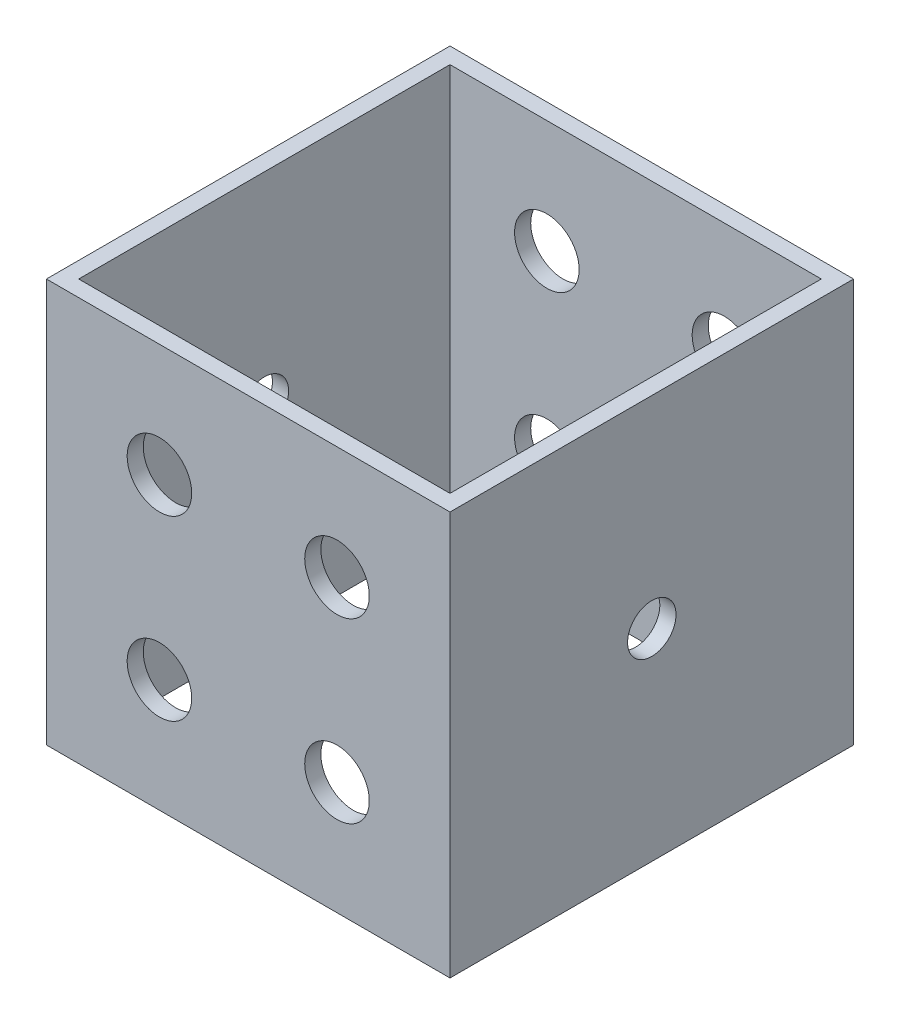
SolidWorks part; units mm, degrees
ref_plane "Front Plane" through (0, 0, 0) normal (0, 0, 1) x (1, 0, 0)
ref_plane "Top Plane" through (0, 0, 0) normal (0, 1, 0) x (1, 0, 0)
ref_plane "Right Plane" through (0, 0, 0) normal (1, 0, 0) x (0, 0, -1)
sketch "Sketch1" plane through (0, 0, 0) normal (0, 1, 0) x (1, 0, 0)
  line L0 (0, 43.992) -> (0, -43.1735) construction
  line L1 (-56.8827, 0) -> (56.8827, 0) construction
  line L3 (-11.5, 11.5) -> (11.5, 11.5)
  line L4 (-11.5, 11.5) -> (-11.5, -11.5)
  line L5 (-11.5, -11.5) -> (11.5, -11.5)
  line L6 (11.5, 11.5) -> (11.5, -11.5)
  line L7 (-11.5, 11.5) -> (11.5, -11.5) construction
  line L8 (-11.5, -11.5) -> (11.5, 11.5) construction
  line L9 (-12.5, 12.5) -> (12.5, 12.5)
  line L10 (-12.5, 12.5) -> (-12.5, -12.5)
  line L11 (-12.5, -12.5) -> (12.5, -12.5)
  line L12 (12.5, 12.5) -> (12.5, -12.5)
  line L13 (-12.5, 12.5) -> (12.5, -12.5) construction
  line L14 (-12.5, -12.5) -> (12.5, 12.5) construction
  point P5 (0, 0)
  point P10 (0, 0)
extrude "Boss-Extrude1" add sketch "Sketch1" along normal blind 12.5 and the other way blind 12.5
sketch "Sketch2" plane through (0, 0, -12.5) normal (0, 0, -1) x (-1, 0, 0)
  line L0 (12.5, -12.5) -> (12.5, 12.5) construction
  line L2 (-12.5, 12.5) -> (12.5, 12.5) construction
  line L6 (-12.5, -12.5) -> (-12.5, 12.5) construction
  circle A0 centre (5.5, 5.5) radius 2
  circle A1 centre (5.5, -5.5) radius 2
  circle A2 centre (-5.5, -5.5) radius 2
  circle A3 centre (-5.5, 5.5) radius 2
  dimension "D1" = 7
  dimension "D2" = 11
  dimension "D3" = 7
  dimension "D4" = 7
  dimension "D5" = 11
  dimension "D6" = 11
  dimension "D7" = 7
  dimension "D8" = 11
extrude "Cut-Extrude1" cut sketch "Sketch2" against normal blind 25
sketch "Sketch3" plane through (12.5, 0, 0) normal (1, 0, 0) x (0, 0, -1)
  circle A0 centre (0, 0) radius 1.5
extrude "Cut-Extrude2" cut sketch "Sketch3" against normal blind 25 contours A0
